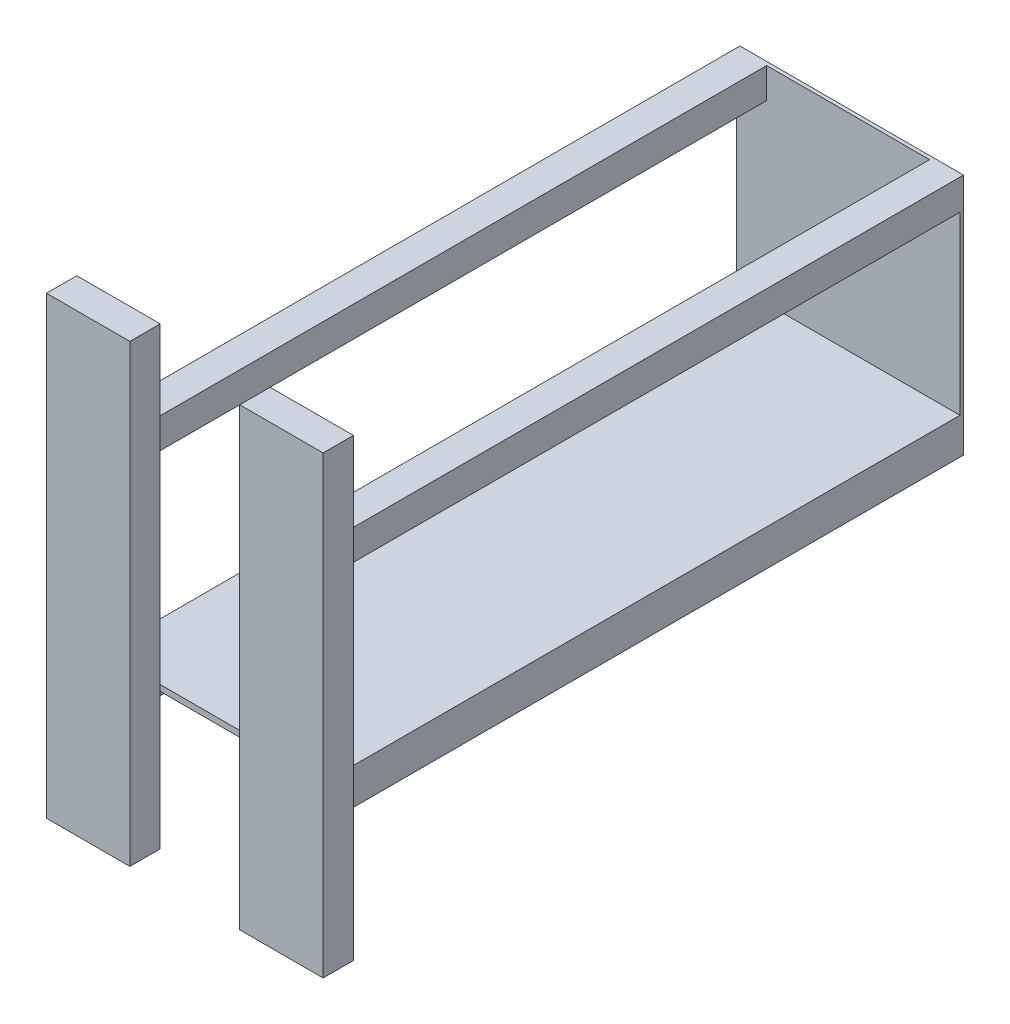
SolidWorks part; units mm, degrees
ref_plane "Front Plane" through (0, 0, 0) normal (0, 0, 1) x (1, 0, 0)
ref_plane "Top Plane" through (0, 0, 0) normal (0, 1, 0) x (1, 0, 0)
ref_plane "Right Plane" through (0, 0, 0) normal (1, 0, 0) x (0, 0, -1)
sketch "Sketch1" plane through (0, 0, 0) normal (0, 0, 1) x (1, 0, 0)
  line L1 (0, 0) -> (374.65, 0)
  line L2 (0, 0) -> (0, 406.4)
  line L3 (0, 406.4) -> (374.65, 406.4)
  line L4 (374.65, 0) -> (374.65, 406.4)
  line L5 (0, 406.4) -> (50.8, 406.4)
  line L6 (0, 406.4) -> (0, 355.6)
  line L7 (0, 355.6) -> (50.8, 355.6)
  line L8 (50.8, 406.4) -> (50.8, 355.6)
  line L9 (0, 0) -> (50.8, 0)
  line L10 (0, 0) -> (0, 50.8)
  line L11 (0, 50.8) -> (50.8, 50.8)
  line L12 (50.8, 0) -> (50.8, 50.8)
  line L13 (374.65, 0) -> (323.85, 0)
  line L14 (374.65, 0) -> (374.65, 50.8)
  line L15 (374.65, 50.8) -> (323.85, 50.8)
  line L16 (323.85, 0) -> (323.85, 50.8)
  line L17 (374.65, 406.4) -> (323.85, 406.4)
  line L18 (374.65, 406.4) -> (374.65, 355.6)
  line L19 (374.65, 355.6) -> (323.85, 355.6)
  line L20 (323.85, 406.4) -> (323.85, 355.6)
  dimension "D1" = 406.4
  dimension "D2" = 374.65
  dimension "D3" = 50.8
  dimension "D4" = 50.8
  dimension "D5" = 50.8
  dimension "D6" = 50.8
  dimension "D7" = 50.8
  dimension "D8" = 50.8
  dimension "D9" = 50.8
  dimension "D10" = 50.8
extrude "Boss-Extrude1" add sketch "Sketch1" along normal blind 6 contours L3 L4 L1 L2
extrude "Boss-Extrude2" add sketch "Sketch1<5>" along normal blind 1066.8 contours L9 L12 L11 L10 | L14 L15 L16 L13 | L17 L20 L19 L18 | L6 L7 L8 L5
sketch "Sketch1<5>" plane through (0, 0, 0) normal (0, 0, 1) x (1, 0, 0) same geometry as "Sketch1"
sketch "Sketch3" plane through (0, 0, 1066.8) normal (0, 0, 1) x (1, 0, 0)
  line L9 (349.25, 0) -> (349.25, 406.4) construction
  line L11 (25.4, 406.4) -> (25.4, 0) construction
  line L13 (0, 406.4) -> (50.8, 406.4) construction
  line L14 (374.65, 355.6) -> (323.85, 355.6) construction
  line L15 (0, 0) -> (50.8, 0) construction
  line L16 (0, 355.6) -> (0, 406.4) construction
  line L17 (374.65, 0) -> (323.85, 0) construction
  line L21 (374.65, 406.4) -> (323.85, 406.4) construction
  line L23 (-44.45, -177.8) -> (95.25, -177.8)
  line L24 (-44.45, -177.8) -> (-44.45, 584.2)
  line L25 (-44.45, 584.2) -> (95.25, 584.2)
  line L26 (95.25, -177.8) -> (95.25, 584.2)
  line L27 (-44.45, -177.8) -> (95.25, 584.2) construction
  line L28 (-44.45, 584.2) -> (95.25, -177.8) construction
  line L29 (279.4, -177.8) -> (419.1, -177.8)
  line L30 (279.4, -177.8) -> (279.4, 584.2)
  line L31 (279.4, 584.2) -> (419.1, 584.2)
  line L32 (419.1, -177.8) -> (419.1, 584.2)
  line L33 (279.4, -177.8) -> (419.1, 584.2) construction
  line L34 (279.4, 584.2) -> (419.1, -177.8) construction
  point P15 (349.25, 0)
  point P16 (25.4, 203.2)
  point P28 (349.25, 203.2)
  dimension "D1" = 139.7
  dimension "D2" = 762
  dimension "D3" = 762
  dimension "D4" = 139.7
extrude "Boss-Extrude4" add sketch "Sketch3" along normal blind 50.8 contours L24 L25 L26 L23 | L30 L31 L32 L29
sketch "Sketch4" plane through (0, 50.8, 0) normal (0, 1, 0) x (1, 0, 0)
  line L1 (0, -6) -> (374.65, -6)
  line L2 (0, -6) -> (0, -1066.8)
  line L3 (0, -1066.8) -> (374.65, -1066.8)
  line L4 (374.65, -6) -> (374.65, -1066.8)
extrude "Boss-Extrude5" add sketch "Sketch4" along normal blind 10
